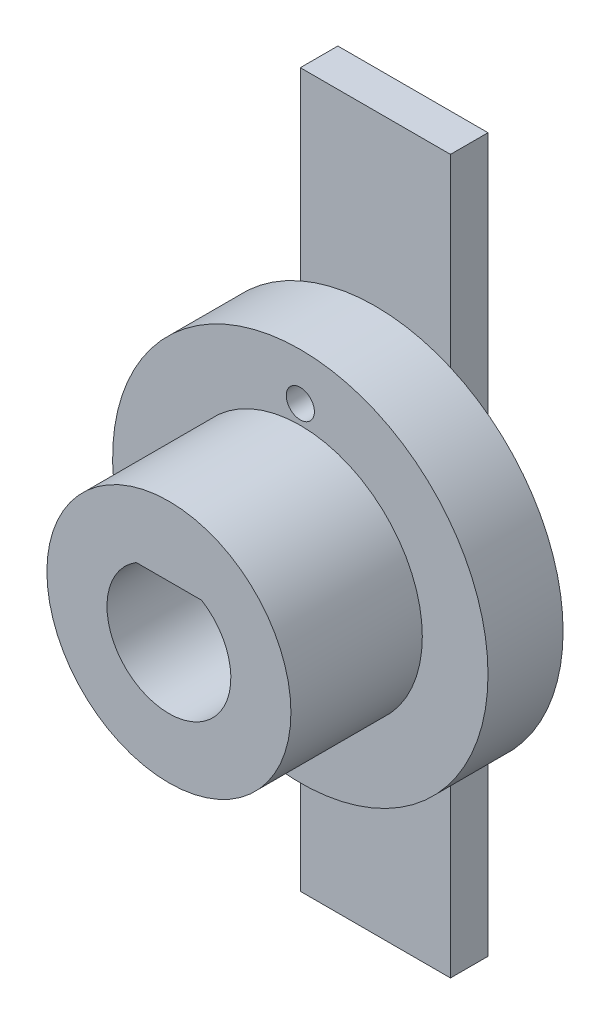
SolidWorks part; units mm, degrees
ref_plane "Plan de face" through (0, 0, 0) normal (0, 0, 1) x (1, 0, 0)
ref_plane "Plan de dessus" through (0, 0, 0) normal (0, 1, 0) x (1, 0, 0)
ref_plane "Plan de droite" through (0, 0, 0) normal (1, 0, 0) x (0, 0, -1)
sketch "Esquisse1" plane through (0, 0, 0) normal (0, 0, 1) x (1, 0, 0)
  line L8 (0, -7.5) -> (0, 7.5) construction
  circle A2 centre (0, -7.5) radius 0.75
  circle A3 centre (0, 7.5) radius 0.75
  circle A4 centre (0, 0) radius 10
  point P6 (0, 0)
  dimension "D2" = 1.5
  dimension "D3" = 1.5
  dimension "D4" = 20
  dimension "D1" = 15
extrude "Boss.-Extru.1" add sketch "Esquisse1" along normal blind 4
sketch "Esquisse2" [suppressed] plane through (0, 0, 10) normal (0, 0, 1) x (1, 0, 0)
  line L0 (-2.2, -2.0396) -> (-2.2, 2.0396)
  line L1 (3, -1.1913) -> (3, 1.3119) construction
  arc A0 (-2.2, -2.0396) -> (-2.2, 2.0396) centre (0, 0) ccw
  dimension "D1" = 6
  dimension "D2" = 5.2
extrude "Enlèv. mat.-Extru.1" [suppressed] cut sketch "Esquisse2" against normal offset from surface (8 mm away) 2 up to face at (10, 0, 0)
sketch "Esquisse3" plane through (0, 0, 4) normal (0, 0, 1) x (1, 0, 0)
  line L0 (-1.7464, 2.8) -> (1.7464, 2.8)
  line L1 (-0.8426, -3.3) -> (1.2459, -3.3) construction
  circle A0 centre (0, 0) radius 6.5
  arc A1 (-1.7464, 2.8) -> (1.7464, 2.8) centre (0, 0) ccw
  dimension "D1" = 6.6
  dimension "D3" = 13
  dimension "D2" = 6.1
extrude "Boss.-Extru.2" add sketch "Esquisse3" along normal blind 7
sketch "Esquisse5" plane through (0, 0, 4) normal (0, 0, 1) x (1, 0, 0)
  line L1 (1.7464, 2.8) -> (-1.7464, 2.8)
  line L2 (1.7464, 2.8) -> (-1.7464, 2.8)
  arc A1 (-1.7464, 2.8) -> (1.7464, 2.8) centre (0, 0) ccw
  arc A2 (-1.7464, 2.8) -> (1.7464, 2.8) centre (0, 0) ccw
  dimension "D1" = 0
extrude "Enlèv. mat.-Extru.2" cut sketch "Esquisse5" against normal offset from surface (2 mm away) 2 up to face at (10, 0, 0)
sketch "Esquisse4" plane through (0, 0, 0) normal (0, 0, -1) x (-1, 0, 0)
  line L1 (-4, 19) -> (4, 19)
  line L2 (-4, 19) -> (-4, -19)
  line L3 (-4, -19) -> (4, -19)
  line L4 (4, 19) -> (4, -19)
  point P4 (0, 19)
  point P5 (-4, 0)
  dimension "D1" = 8
  dimension "D2" = 38
extrude "Boss.-Extru.3" add sketch "Esquisse4" along normal blind 2
